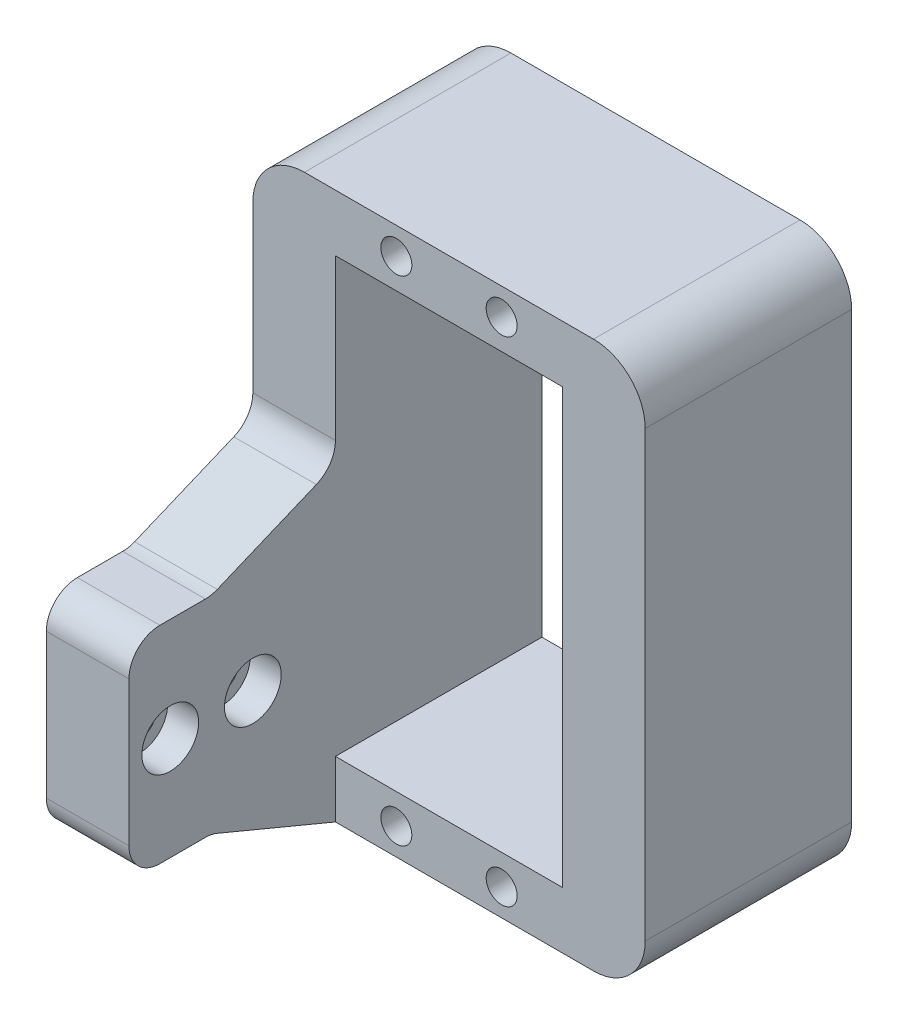
SolidWorks part; units mm, degrees
ref_plane "Front Plane" through (0, 0, 0) normal (0, 0, 1) x (1, 0, 0)
ref_plane "Top Plane" through (0, 0, 0) normal (0, 1, 0) x (1, 0, 0)
ref_plane "Right Plane" through (0, 0, 0) normal (1, 0, 0) x (0, 0, -1)
sketch "Sketch1" plane through (0, 0, 0) normal (0, 0, 1) x (1, 0, 0)
  line L1 (-11, 21) -> (11, 21)
  line L2 (-11, 21) -> (-11, -21)
  line L3 (-11, -21) -> (11, -21)
  line L4 (11, 21) -> (11, -21)
  line L5 (-11, 21) -> (11, -21) construction
  line L6 (-11, -21) -> (11, 21) construction
  line L8 (-19, 26.5) -> (19, 26.5)
  line L9 (-19, 26.5) -> (-19, -26.5)
  line L10 (-19, -26.5) -> (19, -26.5)
  line L11 (19, 26.5) -> (19, -26.5)
  line L12 (-19, 26.5) -> (19, -26.5) construction
  line L13 (-19, -26.5) -> (19, 26.5) construction
  point P0 (0, 0)
  point P6 (0, 0)
  dimension "D1" = 22
  dimension "D2" = 42
  dimension "D4" = 8
  dimension "D3" = 53
extrude "Boss-Extrude1" add sketch "Sketch1" along normal blind 20
sketch "Sketch2" plane through (0, 0, 20) normal (0, 0, 1) x (1, 0, 0)
  line L0 (-19, 26.5) -> (-19, -26.5) construction
  line L1 (-19, -21.5) -> (-11, -21.5)
  line L2 (-19, -21.5) -> (-19, -1.5)
  line L3 (-19, -1.5) -> (-11, -1.5)
  line L4 (-11, -21.5) -> (-11, -1.5)
  line L5 (-11, 21) -> (-11, -21) construction
  line L8 (-19, -26.5) -> (19, -26.5) construction
  point P10 (-15, -21.5)
  dimension "D1" = 20
  dimension "D2" = 5
extrude "Boss-Extrude2" add sketch "Sketch2" along normal blind 20
sketch "Sketch3" plane through (-11, 0, 0) normal (1, 0, 0) x (0, 0, -1)
  line L0 (-40, -21.5) -> (-40, -1.5) construction
  line L1 (-20, -26.5) -> (-20, 26.5) construction
  circle A0 centre (-36, -11.5) radius 2.75
  circle A1 centre (-28, -11.5) radius 2.75
  circle A2 centre (-36, -11.5) radius 1.6
  circle A3 centre (-28, -11.5) radius 1.6
  point P9 (-40, -11.5)
  dimension "D1" = 5.5
  dimension "D4" = 3.2
  dimension "D2" = 4
  dimension "D3" = 8
extrude "Cut-Extrude1" cut sketch "Sketch3" against normal blind 3
extrude "Cut-Extrude2" cut sketch "Sketch3<2>" against normal through all contours A2 | A3 region at (-11, -11.5, 36) region at (-11, -11.5, 28)
sketch "Sketch3<2>" plane through (-11, 0, 0) normal (1, 0, 0) x (0, 0, -1) same geometry as "Sketch3"
sketch "Sketch4" plane through (0, 0, 0) normal (0, 0, -1) x (-1, 0, 0)
  circle A0 centre (-5.1, -23.9) radius 1.5
  circle A1 centre (5.1, -23.9) radius 1.5
  circle A2 centre (-5.1, 23.9) radius 1.5
  circle A3 centre (5.1, 23.9) radius 1.5
  dimension "D1" = 3
extrude "Cut-Extrude3" cut sketch "Sketch4" against normal through all
sketch "Sketch5" plane through (-19, 0, 0) normal (-1, 0, 0) x (0, 0, 1)
  line L0 (20, 26.5) -> (20, -1.5) construction
  line L1 (20, 3.5) -> (32, -1.5)
  line L2 (40, -1.5) -> (20, -1.5) construction
  line L3 (32, -1.5) -> (20, -1.5)
  line L4 (20, -1.5) -> (20, 3.5)
  line L5 (20, -21.5) -> (20, -26.5)
  line L6 (20, -26.5) -> (32, -21.5)
  line L7 (40, -21.5) -> (20, -21.5) construction
  line L8 (32, -21.5) -> (20, -21.5)
  dimension "D1" = 12
extrude "Boss-Extrude3" add sketch "Sketch5" against normal up to surface (8 mm away) up to face at (-11, -11.5, 33.25)
fillet "Fillet1" radius 5 4 edges at (-19, -26.5, 10) (19, -26.5, 10) (-19, 26.5, 10) (19, 26.5, 10)
fillet "Fillet2" radius 3 5 edges at (-15, 3.5, 20) (-15, -21.5, 32) (-15, -1.5, 32) (-15, -21.5, 40) (-15, -1.5, 40)
